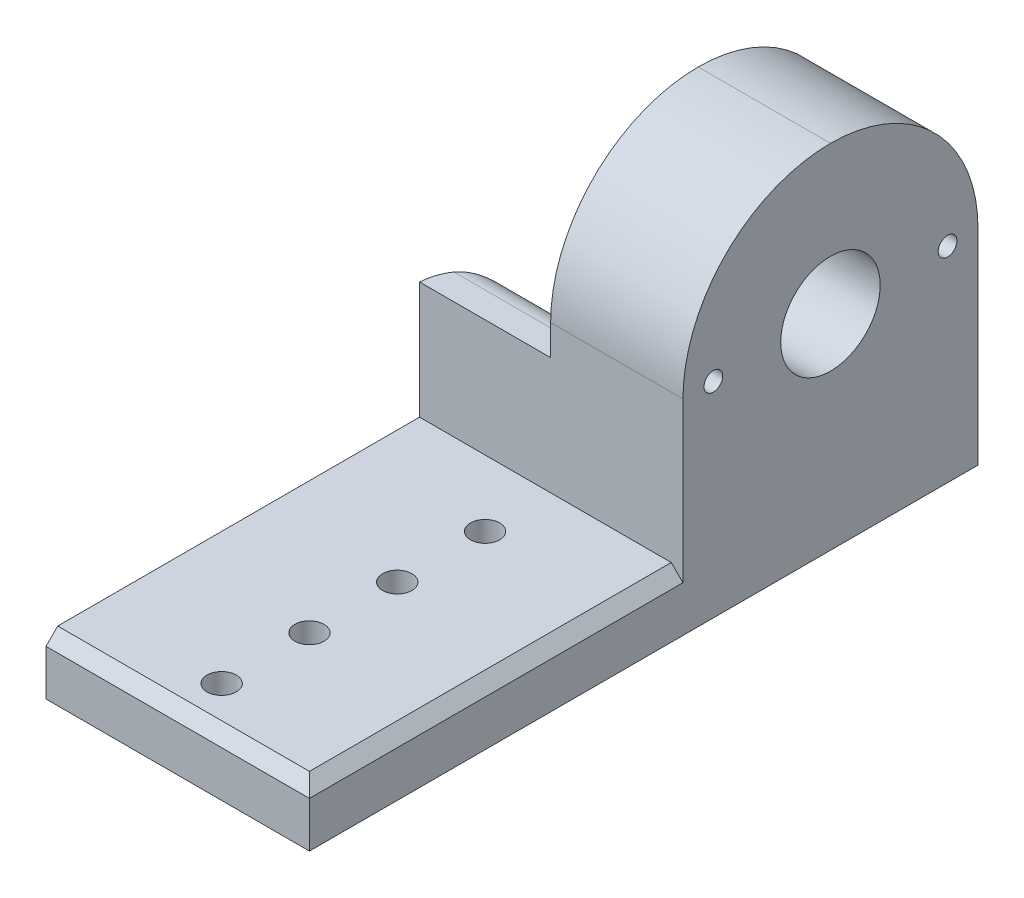
SolidWorks part; units mm, degrees
ref_plane "Front Plane" through (0, 0, 0) normal (0, 0, 1) x (1, 0, 0)
ref_plane "Top Plane" through (0, 0, 0) normal (0, 1, 0) x (1, 0, 0)
ref_plane "Right Plane" through (0, 0, 0) normal (1, 0, 0) x (0, 0, -1)
sketch "Sketch1" plane through (0, 0, 0) normal (0, 1, 0) x (1, 0, 0)
  line L1 (0, 0) -> (57.15, 0)
  line L2 (0, 0) -> (0, 145.034)
  line L3 (0, 145.034) -> (57.15, 145.034)
  line L4 (57.15, 0) -> (57.15, 145.034)
  dimension "D1" = 57.15
  dimension "D2" = 145.034
extrude "Boss-Extrude1" add sketch "Sketch1" along normal blind 25.4
sketch "Sketch3" plane through (57.15, 0, 0) normal (1, 0, 0) x (0, 0, -1)
  line L0 (0, 0) -> (145.034, 0) construction
  line L1 (145.034, 25.4) -> (145.034, 0) construction
  circle A0 centre (113.03, 44.45) radius 32.004
  dimension "D1" = 64.008
  dimension "D2" = 44.45
  dimension "D3" = 32.004
sketch "Sketch4" plane through (0, 0, 0) normal (0, -1, 0) x (-1, 0, 0)
  line L0 (0, 0) -> (-57.15, 0) construction
  line L1 (-57.15, 0) -> (-57.15, 145.034) construction
  circle A0 centre (-28.575, 9.525) radius 3.175
  circle A1 centre (-28.575, 28.575) radius 3.175
  circle A2 centre (-28.575, 47.625) radius 3.175
  circle A3 centre (-28.575, 66.675) radius 3.175
  dimension "D1" = 6.35
  dimension "D2" = 6.35
  dimension "D3" = 6.35
  dimension "D4" = 6.35
  dimension "D5" = 19.05
  dimension "D6" = 19.05
  dimension "D7" = 19.05
  dimension "D8" = 9.525
  dimension "D9" = 28.575
  dimension "D10" = 28.575
  dimension "D11" = 28.575
  dimension "D12" = 28.575
extrude "Cut-Extrude3" cut sketch "Sketch4" against normal through all
sketch "Sketch7" plane through (0, 0, 0) normal (0, -1, 0) x (1, 0, 0)
  line L0 (57.15, 0) -> (57.15, -145.034) construction
  line L1 (57.15, -81.026) -> (28.448, -81.026)
  line L2 (57.15, -81.026) -> (57.15, -145.034)
  line L3 (57.15, -145.034) -> (28.448, -145.034)
  line L4 (28.448, -81.026) -> (28.448, -145.034)
  line L8 (57.15, -145.034) -> (0, -145.034) construction
  dimension "D1" = 28.702
  dimension "D2" = 64.008
  dimension "D3" = 0
extrude "Boss-Extrude2" add sketch "Sketch7" against normal blind 76.454
fillet "Fillet1" radius 32.004 2 edges at (42.799, 76.454, -145.034) (42.799, 76.454, -81.026)
sketch "Sketch9" plane through (28.448, 0, 0) normal (-1, 0, 0) x (0, 0, 1)
  circle A1 centre (-113.03, 44.45) radius 10.795
  circle A2 centre (-138.43, 44.45) radius 2.032
  circle A3 centre (-87.63, 44.45) radius 2.032
  dimension "D1" = 21.59
  dimension "D4" = 4.064
  dimension "D5" = 4.064
  dimension "D2" = 25.4
  dimension "D3" = 25.4
  dimension "D6" = 32.004
  dimension "D7" = 32.004
  dimension "D8" = 32.004
  dimension "D9" = 32.004
extrude "Cut-Extrude5" cut sketch "Sketch9" against normal blind 76.454
sketch "Sketch10" plane through (0, 25.4, 0) normal (0, 1, 0) x (1, 0, 0)
  line L2 (28.448, 113.03) -> (28.448, 81.026)
  line L3 (50.8, 0) -> (0, 0)
  line L4 (0, 113.03) -> (0, 0)
  line L5 (57.15, 81.026) -> (28.448, 81.026)
  line L6 (57.15, 81.026) -> (57.15, 0)
  line L7 (57.15, 0) -> (50.8, 0)
  line L8 (28.448, 145.034) -> (0, 145.034)
  line L9 (28.448, 145.034) -> (28.448, 113.03)
  line L11 (0, 145.034) -> (0, 113.03)
extrude "Cut-Extrude7" cut sketch "Sketch10" against normal blind 12.954
chamfer "Chamfer1" distance 2.54 angle 45 2 edges at (28.575, 12.446, 0) (57.15, 12.446, -40.513)
sketch "Sketch14" plane through (28.448, 0, 0) normal (-1, 0, 0) x (0, 0, 1)
  line L0 (-113.0527, 43.294) -> (-113.03, 44.45) construction
  line L1 (-113.03, 44.45) -> (-113.6572, 12.4521) construction
  line L2 (-81.026, 44.45) -> (-81.026, 12.446) construction
  line L3 (-113.6374, 13.462) -> (-125.3969, 13.462) construction
  line L4 (-145.034, 12.446) -> (-2.54, 12.446) construction
  line L5 (-113.6374, 13.462) -> (-138.0214, 37.846)
  line L6 (-113.6374, 13.462) -> (-89.2534, 37.846)
  line L7 (-113.6374, 13.462) -> (-106.3908, 13.462) construction
  line L8 (-81.026, 12.446) -> (-145.034, 12.446) construction
  line L9 (-138.0214, 37.846) -> (-145.034, 37.846)
  line L10 (-145.034, 44.45) -> (-145.034, 12.446) construction
  line L11 (-145.034, 37.846) -> (-145.034, 12.446)
  line L12 (-145.034, 12.446) -> (-81.026, 12.446)
  line L13 (-81.026, 12.446) -> (-81.026, 37.846)
  line L14 (-81.026, 37.846) -> (-89.2534, 37.846)
  circle A0 centre (-113.03, 44.45) radius 32.004 construction
  dimension "D1" = 1.123
  dimension "D2" = 1.016
  dimension "D3" = 45
  dimension "D4" = 45
  dimension "D5" = 25.4
  dimension "D6" = 25.4
extrude "Boss-Extrude4" add sketch "Sketch14" along normal up to surface (28.448 mm away) up to face at (0, 6.9596, -58.5216)
fillet "Fillet3" radius 6.35 4 edges at (0, 25.654, -101.4454) (0, 25.654, -125.8294) (14.224, 37.846, -89.2534) (14.224, 37.846, -138.0214)
